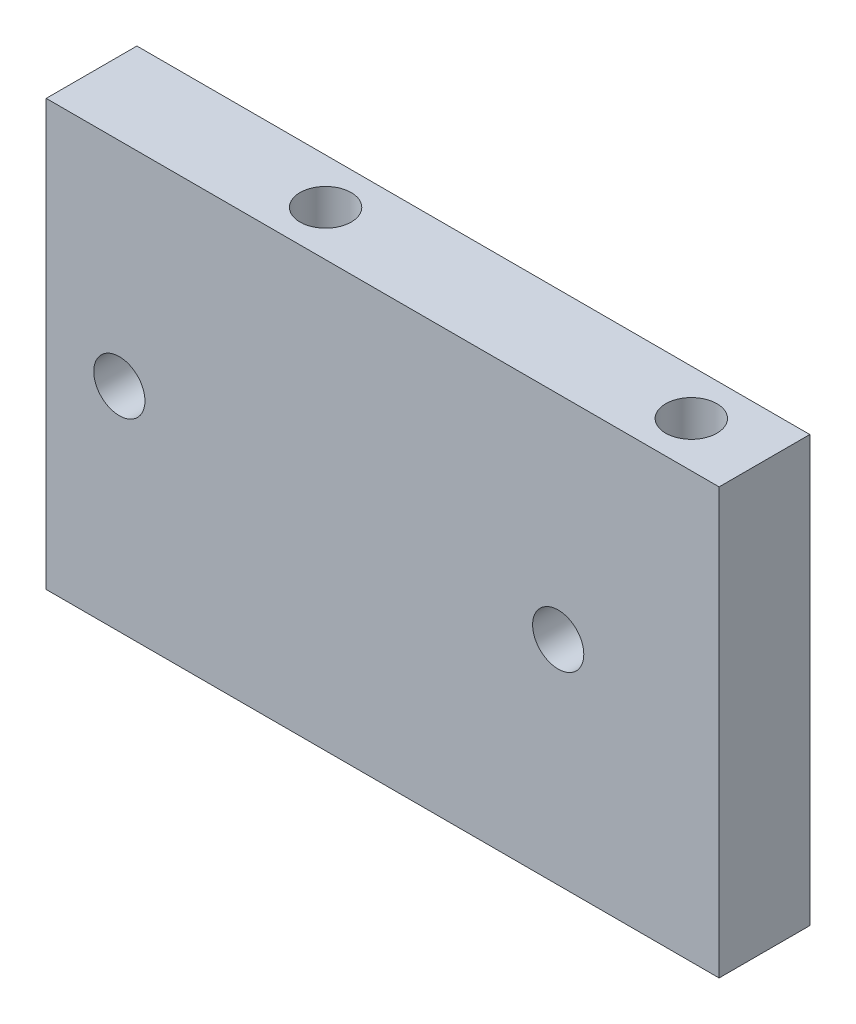
SolidWorks part; units mm, degrees
material "6061 Alloy"
ref_plane "Front Plane" through (0, 0, 0) normal (0, 0, 1) x (1, 0, 0)
ref_plane "Top Plane" through (0, 0, 0) normal (0, 1, 0) x (1, 0, 0)
ref_plane "Right Plane" through (0, 0, 0) normal (1, 0, 0) x (0, 0, -1)
sketch "Sketch1" plane through (0, 0, 0) normal (0, 0, 1) x (1, 0, 0)
  line L1 (-23, 14.5375) -> (23, 14.5375)
  line L2 (-23, 14.5375) -> (-23, -14.5375)
  line L3 (-23, -14.5375) -> (23, -14.5375)
  line L4 (23, 14.5375) -> (23, -14.5375)
  line L5 (0, -14.5375) -> (0, 14.5375) construction
  line L6 (-23, 0) -> (23, 0) construction
  point P0 (0, 0)
  dimension "D1" = 29.075
  dimension "D2" = 46
extrude "1/4" add sketch "Sketch1" along normal blind 6.2
sketch "Sketch2" plane through (0, 0, 0) normal (0, 0, 1) x (1, 0, 0)
  line L0 (0, 0) -> (-18, 0) construction
  line L1 (0, 0) -> (0, 8.9877) construction
  line L2 (-23, 14.5375) -> (-23, -14.5375) construction
  circle A0 centre (-18, 0) radius 1.75
  circle A2 centre (12, 0) radius 1.75
  dimension "D2" = 3.5
  dimension "D1" = 5
  dimension "D3" = 2
extrude "M4_DRILL" cut sketch "Sketch2" along normal up to surface (6.2 mm away) up to face at (0, 0, 6.2)
sketch "Sketch3" plane through (0, -14.5375, 0) normal (0, -1, 0) x (1, 0, 0)
  line L0 (-23, 3.1) -> (-7, 3.1) construction
  line L1 (-23, 6.2) -> (-23, 0) construction
  circle A0 centre (-7, 3.1) radius 1.75
  circle A1 centre (18, 3.1) radius 1.75
  dimension "D1" = 3.5
  dimension "D2" = 16
  dimension "D4" = 25
  dimension "D3" = 2
extrude "M4_DRILL2" cut sketch "Sketch3" against normal blind 8
sketch "Sketch4" plane through (0, 14.5375, 0) normal (0, 1, 0) x (1, 0, 0)
  circle A0 centre (18, -3.1) radius 1.75 construction
  circle A1 centre (-7, -3.1) radius 1.75 construction
  circle A2 centre (18, -3.1) radius 1.75
  circle A3 centre (-7, -3.1) radius 1.75
extrude "M4_DRILL3" cut sketch "Sketch4" against normal blind 8
